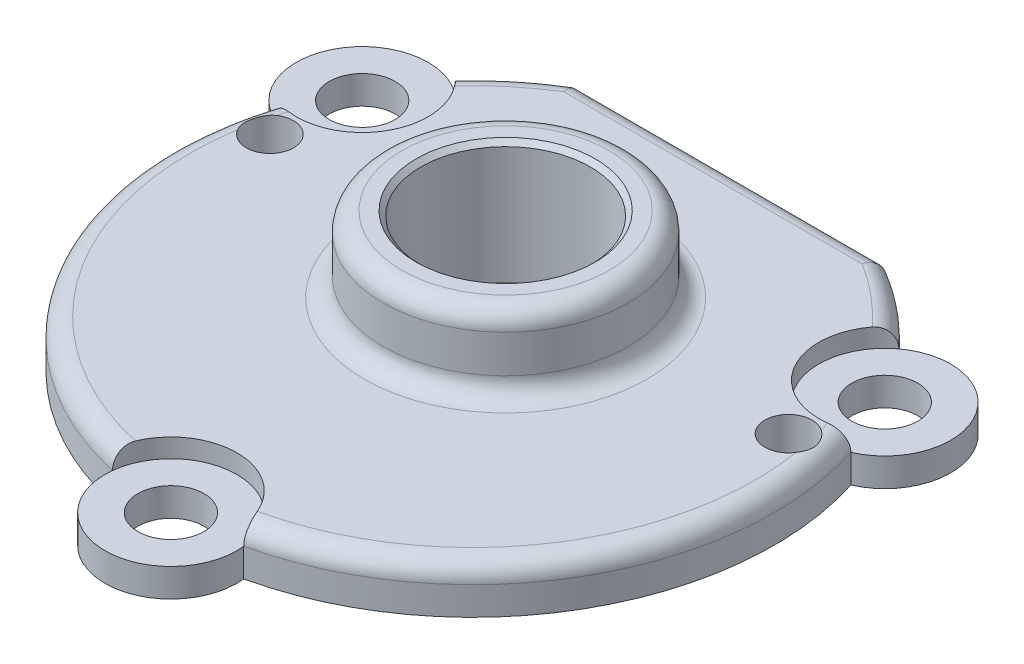
SolidWorks part; units mm, degrees
ref_plane "前视基准面" through (0, 0, 0) normal (0, 0, 1) x (1, 0, 0)
ref_plane "上视基准面" through (0, 0, 0) normal (0, 1, 0) x (1, 0, 0)
ref_plane "右视基准面" through (0, 0, 0) normal (1, 0, 0) x (0, 0, -1)
other "Configuration Table"
sketch "草图1" plane through (0, 0, 0) normal (0, 1, 0) x (1, 0, 0)
  line L0 (-16.3631, 27.5) -> (16.3631, 27.5)
  arc A0 (-16.3631, 27.5) -> (16.3631, 27.5) centre (0, 0) ccw
  dimension "D1" = 27.5
  dimension "D2" = 32
extrude "凸台-拉伸1" add sketch "草图1" along normal blind 5
fillet "圆角2" radius 2 2 edges at (0, 5, 32) (0, 5, -27.5)
sketch "草图2" plane through (0, 5, 0) normal (0, 1, 0) x (1, 0, 0)
  circle A0 centre (0, -32) radius 7
  arc A1 (16.3631, 27.5) -> (-16.3631, 27.5) centre (0, 0) ccw construction
  circle A2 centre (-27.7128, 16) radius 7
  circle A3 centre (27.7128, 16) radius 7
  point P5 (32.8449, 21.4626)
  point P12 (0, 0)
  dimension "D1" = 14
  dimension "D2" = 3
extrude "凸台-拉伸2" add sketch "草图2" against normal blind 5
extrude "切除-拉伸1" cut sketch "草图2<2>" against normal blind 2
sketch "草图2<2>" plane through (0, 5, 0) normal (0, 1, 0) x (1, 0, 0) same geometry as "草图2"
sketch "草图3" plane through (0, 3, 0) normal (0, 1, 0) x (1, 0, 0)
  circle A0 centre (0, -32) radius 3.5
  circle A1 centre (-27.7128, 16) radius 3.5
  arc A2 (6.958, -31.2344) -> (-6.958, -31.2344) centre (0, -32) ccw
  arc A3 (-6.958, -31.2344) -> (6.958, -31.2344) centre (0, -32) ccw
  arc A4 (6.958, -31.2344) -> (-6.958, -31.2344) centre (0, -32) ccw construction
  arc A5 (-6.958, -31.2344) -> (6.958, -31.2344) centre (0, -32) ccw construction
  circle A6 centre (27.7128, 16) radius 3.5
  point P3 (31.4897, 17.6788)
  point P12 (0, 0)
  dimension "D2" = 7
  dimension "D1" = 0
  dimension "D3" = 3
extrude "切除-拉伸2" cut sketch "草图3" against normal through all
sketch "草图4" plane through (0, 0, 0) normal (0, 1, 0) x (1, 0, 0)
  circle A0 centre (0, 3.5) radius 13
  dimension "D1" = 26
  dimension "D2" = 3.5
extrude "凸台-拉伸3" add sketch "草图4" along normal blind 13
sketch "草图5" plane through (0, 13, 0) normal (0, 1, 0) x (1, 0, 0)
  circle A0 centre (0, 3.5) radius 9
  circle A1 centre (0, 3.5) radius 13
  circle A2 centre (0, 3.5) radius 13
  dimension "D2" = 18
  dimension "D1" = 0
extrude "切除-拉伸3" cut sketch "草图5" against normal through all contours A0 region at (0, 13, -3.5)
sketch "草图6" plane through (0, 5, 0) normal (0, 1, 0) x (1, 0, 0)
  line L0 (0, 0) -> (0, 10.8937) construction
  circle A0 centre (27.5, 6) radius 2.5
  circle A1 centre (-27.5, 6) radius 2.5
  point P9 (-4.7553, -1.9225)
  dimension "D1" = 5
  dimension "D2" = 55
  dimension "D3" = 6
extrude "切除-拉伸4" cut sketch "草图6" against normal through all
chamfer "倒角1" distance 0.5 angle 45 1 edges at (0, 13, 5.5)
fillet "圆角1" radius 2 2 edges at (0, 5, 9.5) (0, 13, 9.5)
